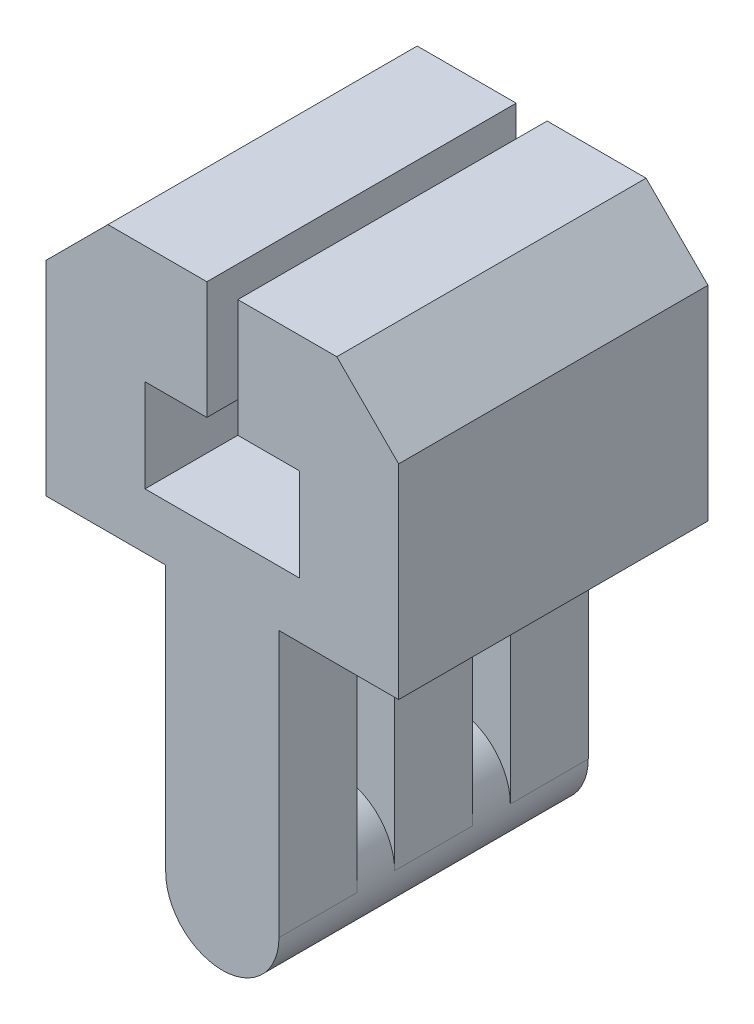
SolidWorks part; units mm, degrees
material "6061-T6 (SS)"
ref_plane "Front Plane" through (0, 0, 0) normal (0, 0, 1) x (1, 0, 0)
ref_plane "Top Plane" through (0, 0, 0) normal (0, 1, 0) x (1, 0, 0)
ref_plane "Right Plane" through (0, 0, 0) normal (1, 0, 0) x (0, 0, -1)
sketch "Sketch1" plane through (0, 0, 0) normal (0, 0, 1) x (1, 0, 0)
  circle A0 centre (0, 0) radius 23.241
  dimension "D1" = 46.482
extrude "ftA" add sketch "Sketch1" against normal blind 127 contours A0
sketch "Sketch2" plane through (0, 0, -127) normal (0, 0, -1) x (-1, 0, 0)
  line L1 (-23.241, 0) -> (23.241, 0)
  line L2 (-23.241, 0) -> (-23.241, 101.6)
  line L3 (-23.241, 101.6) -> (23.241, 101.6)
  line L4 (23.241, 0) -> (23.241, 101.6)
  circle A0 centre (0, 0) radius 23.241 construction
  dimension "D1" = 46.482
  dimension "D2" = 101.6
extrude "ftB" add sketch "Sketch2" against normal blind 32.004 separate body
sketch "Sketch3" plane through (0, 0, -127) normal (0, 0, -1) x (-1, 0, 0)
  line L0 (-23.241, 101.6) -> (-31.75, 101.6)
  line L9 (-31.75, 101.6) -> (-31.75, 132.08)
  line L10 (-31.75, 132.08) -> (31.75, 132.08)
  line L11 (31.75, 132.08) -> (31.75, 101.6)
  line L12 (31.75, 101.6) -> (23.241, 101.6)
  line L13 (23.241, 101.6) -> (-23.241, 101.6)
  dimension "D1" = 63.5
  dimension "D2" = 30.48
extrude "ftC" add sketch "Sketch3" against normal blind 127 contours L13 L0 L9 L10 L11 L12
sketch "Sketch4" plane through (0, 0, 0) normal (0, 0, 1) x (1, 0, 0)
  line L9 (-31.75, 132.08) -> (-72.39, 132.08)
  line L10 (-31.75, 132.08) -> (-31.75, 170.18)
  line L11 (-31.75, 170.18) -> (-72.39, 170.18)
  line L12 (-72.39, 132.08) -> (-72.39, 170.18)
  line L13 (31.75, 132.08) -> (72.39, 132.08)
  line L14 (31.75, 132.08) -> (31.75, 170.18)
  line L15 (31.75, 170.18) -> (72.39, 170.18)
  line L16 (72.39, 132.08) -> (72.39, 170.18)
  dimension "D1" = 40.64
  dimension "D2" = 38.1
extrude "ftD1" add sketch "Sketch4" against normal blind 127 separate body contours L15 L16 L13 L14
extrude "ftD2" add sketch "Sketch4<5>" against normal blind 127
sketch "Sketch4<5>" plane through (0, 0, 0) normal (0, 0, 1) x (1, 0, 0) same geometry as "Sketch4"
sketch "Sketch5" plane through (0, 0, 0) normal (0, 0, 1) x (1, 0, 0)
  line L1 (-31.75, 170.18) -> (-6.35, 170.18)
  line L2 (-31.75, 170.18) -> (-31.75, 218.44)
  line L3 (-31.75, 218.44) -> (-6.35, 218.44)
  line L4 (-6.35, 170.18) -> (-6.35, 218.44)
  line L5 (31.75, 170.18) -> (6.35, 170.18)
  line L6 (31.75, 170.18) -> (31.75, 218.44)
  line L7 (31.75, 218.44) -> (6.35, 218.44)
  line L8 (6.35, 170.18) -> (6.35, 218.44)
  dimension "D1" = 48.26
  dimension "D2" = 25.4
extrude "ftE" add sketch "Sketch5" against normal blind 127 separate body
sketch "Sketch6" plane through (0, 0, 0) normal (0, 0, 1) x (1, 0, 0)
  line L0 (-31.75, 101.6) -> (31.75, 101.6) construction
  line L5 (31.75, 218.44) -> (72.39, 218.44)
  line L6 (31.75, 218.44) -> (31.75, 170.18)
  line L7 (31.75, 170.18) -> (72.39, 170.18)
  line L8 (72.39, 218.44) -> (72.39, 170.18)
  line L13 (-31.75, 218.44) -> (-72.39, 218.44)
  line L14 (-31.75, 218.44) -> (-31.75, 170.18)
  line L15 (-31.75, 170.18) -> (-72.39, 170.18)
  line L16 (-72.39, 218.44) -> (-72.39, 170.18)
  line L17 (-72.39, 132.08) -> (-31.75, 132.08)
  line L18 (-72.39, 132.08) -> (-72.39, 101.6)
  line L19 (-72.39, 101.6) -> (-31.75, 101.6)
  line L20 (-31.75, 132.08) -> (-31.75, 101.6)
  line L21 (31.75, 101.6) -> (72.39, 101.6)
  line L22 (31.75, 101.6) -> (31.75, 132.08)
  line L23 (31.75, 132.08) -> (72.39, 132.08)
  line L24 (72.39, 101.6) -> (72.39, 132.08)
extrude "Filler" add sketch "Sketch6" against normal blind 127
combine bodies "Combine3" operation type add bodies to combine 109 101
ref_plane "Plane1" through (0, 0, -63.5) normal (0, 0, 1) x (1, 0, 0)
sketch "Sketch8" plane through (0, 0, -63.5) normal (0, 0, 1) x (1, 0, 0)
  line L0 (-23.241, 0) -> (23.241, 0)
  line L1 (23.241, 0) -> (23.241, 101.6)
  line L2 (23.241, 101.6) -> (-23.241, 101.6)
  line L3 (-23.241, 101.6) -> (-23.241, 0)
extrude "Boss-Extrude1" add sketch "Sketch8" along normal blind 16.002 and the other way blind 16.002
chamfer "Chamfer1" distance 7.62 angle 45 10 edges at (23.241, 101.6, -110.998) (0, 101.6, -94.996) (-23.241, 101.6, -110.998) (-23.241, 101.6, -63.5) (0, 101.6, -79.502) (23.241, 101.6, -63.5) (0, 101.6, -47.498) (-72.39, 101.6, -63.5) (0, 101.6, 0) (72.39, 101.6, -63.5)
sketch "Sketch9" plane through (0, 0, 0) normal (0, 0, 1) x (1, 0, 0)
  line L0 (-23.241, 0) -> (23.241, 0)
  line L1 (-23.241, 0) -> (-23.241, 101.6)
  line L2 (-30.861, 101.6) -> (30.861, 101.6) construction
  line L4 (64.77, 101.6) -> (-64.77, 101.6) construction
  line L5 (23.241, 101.6) -> (23.241, 0)
  line L6 (-23.241, 101.6) -> (-23.241, 109.22)
  line L7 (-72.39, 109.22) -> (72.39, 109.22) construction
  line L8 (-23.241, 109.22) -> (23.241, 109.22)
  line L9 (23.241, 109.22) -> (23.241, 101.6)
  circle A0 centre (0, 0) radius 23.241 construction
extrude "Boss-Extrude2" add sketch "Sketch9" against normal blind 32.004
chamfer "Chamfer2" distance 25.4 angle 45 2 edges at (-72.39, 218.44, -63.5) (72.39, 218.44, -63.5)
chamfer "Chamfer3" distance 7.62 angle 45 3 edges at (-23.241, 101.6, -19.812) (23.241, 101.6, -19.812) (0, 101.6, -32.004)
equation "\"F\"= 600'Applied force"
equation "\"Yst\"= 39885.32'Yield strength"
equation "\"Sf\"= 4'Safety factor"
equation "\"def\"= .005'Deflection"
equation "\"Lst\"= 5'Length of strap"
equation "\"E\"= 10007604'Modulus of elasticity"
equation "\"Dst\"= ( ( \"F\" * \"Lst\" * \"Sf\" * 32 * 2 ) / ( \"Yst\" * 3.14159 ) ) ^ ( 1 / 3 )'Driven diameter of feauture A"
equation "\"Lftb\"= 4'Chosen length of feature B"
equation "\"hftb\"= ( ( \"F\" * \"Lftb\" * \"Sf\" * 6 * 2 ) / ( \"Dst\" * \"Yst\" ) ) ^ ( 1 / 2 )'Driven height of feature B"
equation "\"Bftc\"= 2.5'Base of feature C, from T-beam dim"
equation "\"hftc\"= ( ( \"F\" * \"Lst\" * \"Sf\" * 2 * 6 ) / ( \"Bftc\" * \"Yst\" ) ) ^ ( 1 / 2 )'Driven height of feature C"
equation "\"hftd\"= 1.5'Chosen height of feature D"
equation "\"cftd\"= \"hftd\" / 2'Neutral axis of feature D (distance)"
equation "\"bftd\"= ( \"F\" * \"Lst\" * \"cftd\" * \"Sf\" * 2 * 12 ) / ( \"Yst\" * ( \"hftd\" ^ 3 ) )'Driven base of feature D"
equation "\"bfte\"= 1'Base of feature E, from T-beam dim"
equation "\"hfte\"= ( ( \"F\" * \"Lst\" * \"Sf\" * 6 * 2 ) / ( \"Yst\" * \"bfte\" ) ) ^ ( 1 / 2 )'Driven height of feature E"
equation "\"hlink\"= 6'Chosen height of link"
equation "\"blink\"= 2.25'Chosen base of link"
equation "\"clink\"= 3'Neutral axis of link (distance)"
equation "\"tlink\"= ( \"F\" * \"hlink\" * \"clink\" * \"Sf\" * 12 * 2 ) / ( \"Yst\" * ( \"hlink\" ^ 3 ) )'Driven thickness of link"
